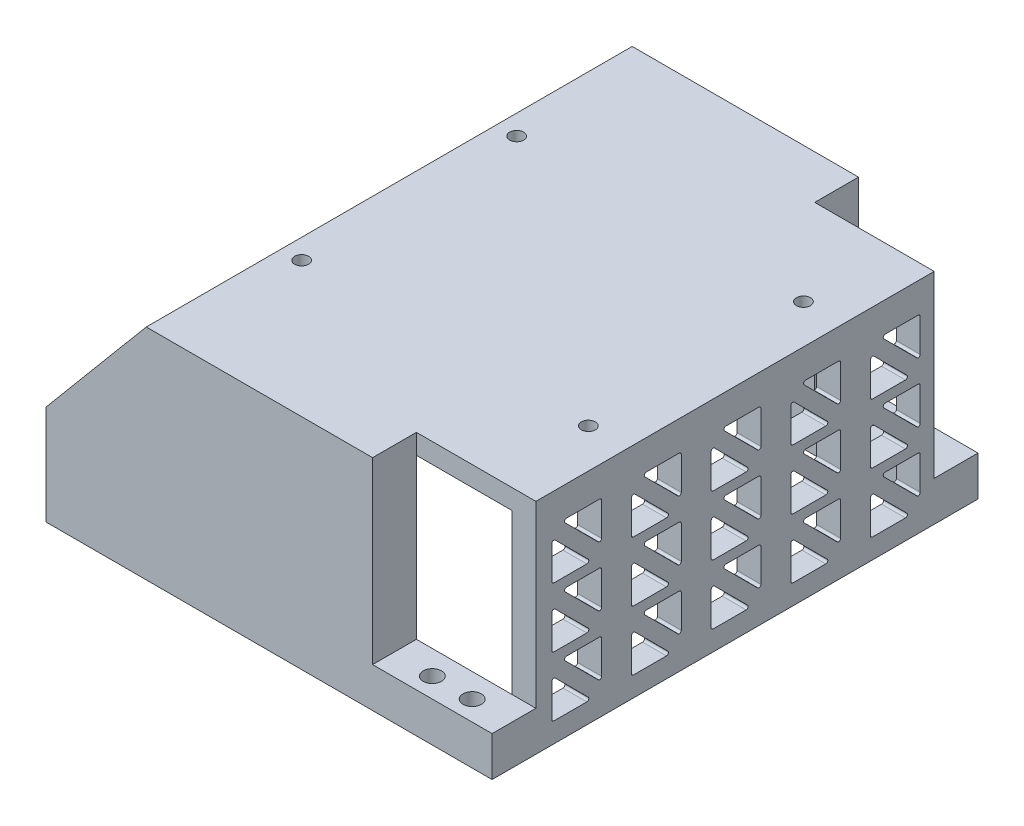
SolidWorks part; units mm, degrees
ref_plane "Front Plane" through (0, 0, 0) normal (0, 0, 1) x (1, 0, 0)
ref_plane "Top Plane" through (0, 0, 0) normal (0, 1, 0) x (1, 0, 0)
ref_plane "Right Plane" through (0, 0, 0) normal (1, 0, 0) x (0, 0, -1)
sketch "Sketch1" plane through (0, 0, 0) normal (0, 1, 0) x (1, 0, 0)
  line L0 (56, 61) -> (64.4545, 61) construction
  line L1 (0, 0) -> (112, 0)
  line L2 (0, 0) -> (0, 122)
  line L3 (0, 122) -> (112, 122)
  line L4 (112, 0) -> (112, 122)
  line L5 (0, 0) -> (112, 122) construction
  line L6 (0, 122) -> (112, 0) construction
  line L7 (106, 11) -> (112, 11)
  line L13 (26, 11) -> (106, 11)
  line L14 (82, 11) -> (82, 0)
  line L15 (82, 111) -> (82, 122)
  line L16 (106, 111) -> (112, 111)
  line L17 (26, 11) -> (26, 111)
  line L18 (26, 111) -> (106, 111)
  line L19 (106, 11) -> (106, 111)
  line L20 (26, 11) -> (106, 111) construction
  line L21 (26, 111) -> (106, 11) construction
  circle A0 centre (102, 5) radius 2.3
  circle A1 centre (92, 5) radius 2.3
  circle A2 centre (92, 117) radius 2.3
  circle A3 centre (102, 117) radius 2.3
  point P4 (56, 61)
  point P28 (66, 61)
  point P29 (0, 0)
  point P30 (0, 0)
  point P31 (0, 0)
  dimension "D3" = 4.6
  dimension "D1" = 122
  dimension "D2" = 112
  dimension "D4" = 10
  dimension "D5" = 5
  dimension "D6" = 10
  dimension "D7" = 100
  dimension "D8" = 80
  dimension "D9" = 30
extrude "Boss-Extrude1" add sketch "Sketch1" along normal blind 50 contours L15 L3 L2 L1 L14 | L16 L7 L4 region at (24.4696, 0, -61) region at (109, 0, -61)
extrude "Boss-Extrude2" add sketch "Sketch1<3>" along normal blind 10 contours L16 L4 L3 L15 A2 A3 | L14 L1 L4 L7 A1 A0 region at (97, 0, -5.556) region at (97, 0, -116.444)
sketch "Sketch1<3>" plane through (0, 0, 0) normal (0, 1, 0) x (1, 0, 0) same geometry as "Sketch1"
sketch "Sketch2" plane through (112, 0, 0) normal (1, 0, 0) x (0, 0, -1)
  line L54 (0, 0) -> (122, 0) construction
  line L55 (11, 50) -> (111, 50) construction
  line L56 (11, 50) -> (11, 0) construction
  line L57 (11, 0) -> (111, 0) construction
  line L58 (111, 50) -> (111, 0) construction
  line L59 (11, 50) -> (111, 0) construction
  line L60 (11, 0) -> (111, 50) construction
  line L61 (111, 50) -> (111, 10) construction
  line L62 (15, 35.5) -> (15, 43.7929)
  line L63 (15.8536, 44.1464) -> (24.1464, 35.8536)
  line L64 (23.7929, 35) -> (15.5, 35)
  line L65 (27.5, 38.7071) -> (27.5, 47)
  line L66 (27, 47.5) -> (18.7071, 47.5)
  line L67 (18.3536, 46.6464) -> (26.6464, 38.3536)
  line L68 (43.7929, 35) -> (35.5, 35)
  line L69 (15, 35) -> (27.5, 35) construction
  line L70 (15, 35) -> (15, 47.5) construction
  line L71 (15, 47.5) -> (27.5, 47.5) construction
  line L72 (27.5, 35) -> (27.5, 47.5) construction
  line L73 (15, 35) -> (27.5, 47.5) construction
  line L74 (15, 47.5) -> (27.5, 35) construction
  line L75 (35, 35.5) -> (35, 43.7929)
  line L76 (35.8536, 44.1464) -> (44.1464, 35.8536)
  line L77 (38.3536, 46.6464) -> (46.6464, 38.3536)
  line L78 (47.5, 38.7071) -> (47.5, 47)
  line L79 (47, 47.5) -> (38.7071, 47.5)
  line L80 (63.7929, 35) -> (55.5, 35)
  line L81 (55, 35.5) -> (55, 43.7929)
  line L82 (55.8536, 44.1464) -> (64.1464, 35.8536)
  line L83 (58.3536, 46.6464) -> (66.6464, 38.3536)
  line L84 (67.5, 38.7071) -> (67.5, 47)
  line L85 (67, 47.5) -> (58.7071, 47.5)
  line L86 (83.7929, 35) -> (75.5, 35)
  line L87 (75, 35.5) -> (75, 43.7929)
  line L88 (75.8536, 44.1464) -> (84.1464, 35.8536)
  line L89 (78.3536, 46.6464) -> (86.6464, 38.3536)
  line L90 (87.5, 38.7071) -> (87.5, 47)
  line L91 (87, 47.5) -> (78.7071, 47.5)
  line L92 (103.7929, 35) -> (95.5, 35)
  line L93 (95, 35.5) -> (95, 43.7929)
  line L94 (95.8536, 44.1464) -> (104.1464, 35.8536)
  line L95 (98.3536, 46.6464) -> (106.6464, 38.3536)
  line L96 (107.5, 38.7071) -> (107.5, 47)
  line L97 (107, 47.5) -> (98.7071, 47.5)
  line L98 (43.7929, 20) -> (35.5, 20)
  line L99 (35, 20.5) -> (35, 28.7929)
  line L100 (35.8536, 29.1464) -> (44.1464, 20.8536)
  line L101 (38.3536, 31.6464) -> (46.6464, 23.3536)
  line L102 (47.5, 23.7071) -> (47.5, 32)
  line L103 (47, 32.5) -> (38.7071, 32.5)
  line L104 (63.7929, 20) -> (55.5, 20)
  line L105 (55, 20.5) -> (55, 28.7929)
  line L106 (55.8536, 29.1464) -> (64.1464, 20.8536)
  line L107 (58.3536, 31.6464) -> (66.6464, 23.3536)
  line L108 (67.5, 23.7071) -> (67.5, 32)
  line L109 (67, 32.5) -> (58.7071, 32.5)
  line L110 (83.7929, 20) -> (75.5, 20)
  line L111 (75, 20.5) -> (75, 28.7929)
  line L112 (75.8536, 29.1464) -> (84.1464, 20.8536)
  line L113 (78.3536, 31.6464) -> (86.6464, 23.3536)
  line L114 (87.5, 23.7071) -> (87.5, 32)
  line L115 (87, 32.5) -> (78.7071, 32.5)
  line L116 (103.7929, 20) -> (95.5, 20)
  line L117 (95, 20.5) -> (95, 28.7929)
  line L118 (95.8536, 29.1464) -> (104.1464, 20.8536)
  line L119 (98.3536, 31.6464) -> (106.6464, 23.3536)
  line L120 (107.5, 23.7071) -> (107.5, 32)
  line L121 (107, 32.5) -> (98.7071, 32.5)
  line L122 (43.7929, 5) -> (35.5, 5)
  line L123 (35, 5.5) -> (35, 13.7929)
  line L124 (35.8536, 14.1464) -> (44.1464, 5.8536)
  line L125 (38.3536, 16.6464) -> (46.6464, 8.3536)
  line L126 (47.5, 8.7071) -> (47.5, 17)
  line L127 (47, 17.5) -> (38.7071, 17.5)
  line L128 (63.7929, 5) -> (55.5, 5)
  line L129 (55, 5.5) -> (55, 13.7929)
  line L130 (55.8536, 14.1464) -> (64.1464, 5.8536)
  line L131 (58.3536, 16.6464) -> (66.6464, 8.3536)
  line L132 (67.5, 8.7071) -> (67.5, 17)
  line L133 (67, 17.5) -> (58.7071, 17.5)
  line L134 (83.7929, 5) -> (75.5, 5)
  line L135 (75, 5.5) -> (75, 13.7929)
  line L136 (75.8536, 14.1464) -> (84.1464, 5.8536)
  line L137 (78.3536, 16.6464) -> (86.6464, 8.3536)
  line L138 (87.5, 8.7071) -> (87.5, 17)
  line L139 (87, 17.5) -> (78.7071, 17.5)
  line L140 (103.7929, 5) -> (95.5, 5)
  line L141 (95, 5.5) -> (95, 13.7929)
  line L142 (95.8536, 14.1464) -> (104.1464, 5.8536)
  line L143 (98.3536, 16.6464) -> (106.6464, 8.3536)
  line L144 (107.5, 8.7071) -> (107.5, 17)
  line L145 (107, 17.5) -> (98.7071, 17.5)
  line L146 (23.7929, 20) -> (15.5, 20)
  line L147 (15, 20.5) -> (15, 28.7929)
  line L148 (15.8536, 29.1464) -> (24.1464, 20.8536)
  line L149 (18.3536, 31.6464) -> (26.6464, 23.3536)
  line L150 (27.5, 23.7071) -> (27.5, 32)
  line L151 (27, 32.5) -> (18.7071, 32.5)
  line L152 (23.7929, 5) -> (15.5, 5)
  line L153 (15, 5.5) -> (15, 13.7929)
  line L154 (15.8536, 14.1464) -> (24.1464, 5.8536)
  line L155 (18.3536, 16.6464) -> (26.6464, 8.3536)
  line L156 (27.5, 8.7071) -> (27.5, 17)
  line L157 (27, 17.5) -> (18.7071, 17.5)
  line L158 (23.7929, 35) -> (43.7929, 35) construction
  line L159 (23.7929, 35) -> (23.7929, 20) construction
  arc A0 (27, 47.5) -> (27.5, 47) centre (27, 47) cw
  arc A1 (27.5, 38.7071) -> (26.6464, 38.3536) centre (27, 38.7071) cw
  arc A2 (24.1464, 35.8536) -> (23.7929, 35) centre (23.7929, 35.5) cw
  arc A3 (15, 35.5) -> (15.5, 35) centre (15.5, 35.5) ccw
  arc A4 (15, 43.7929) -> (15.8536, 44.1464) centre (15.5, 43.7929) cw
  arc A5 (18.7071, 47.5) -> (18.3536, 46.6464) centre (18.7071, 47) ccw
  arc A6 (35, 35.5) -> (35.5, 35) centre (35.5, 35.5) ccw
  arc A7 (44.1464, 35.8536) -> (43.7929, 35) centre (43.7929, 35.5) cw
  arc A8 (35, 43.7929) -> (35.8536, 44.1464) centre (35.5, 43.7929) cw
  arc A9 (38.7071, 47.5) -> (38.3536, 46.6464) centre (38.7071, 47) ccw
  arc A10 (47.5, 38.7071) -> (46.6464, 38.3536) centre (47, 38.7071) cw
  arc A11 (47, 47.5) -> (47.5, 47) centre (47, 47) cw
  arc A12 (55, 35.5) -> (55.5, 35) centre (55.5, 35.5) ccw
  arc A13 (64.1464, 35.8536) -> (63.7929, 35) centre (63.7929, 35.5) cw
  arc A14 (55, 43.7929) -> (55.8536, 44.1464) centre (55.5, 43.7929) cw
  arc A15 (58.7071, 47.5) -> (58.3536, 46.6464) centre (58.7071, 47) ccw
  arc A16 (67.5, 38.7071) -> (66.6464, 38.3536) centre (67, 38.7071) cw
  arc A17 (67, 47.5) -> (67.5, 47) centre (67, 47) cw
  arc A18 (75, 35.5) -> (75.5, 35) centre (75.5, 35.5) ccw
  arc A19 (84.1464, 35.8536) -> (83.7929, 35) centre (83.7929, 35.5) cw
  arc A20 (75, 43.7929) -> (75.8536, 44.1464) centre (75.5, 43.7929) cw
  arc A21 (78.7071, 47.5) -> (78.3536, 46.6464) centre (78.7071, 47) ccw
  arc A22 (87.5, 38.7071) -> (86.6464, 38.3536) centre (87, 38.7071) cw
  arc A23 (87, 47.5) -> (87.5, 47) centre (87, 47) cw
  arc A24 (95, 35.5) -> (95.5, 35) centre (95.5, 35.5) ccw
  arc A25 (104.1464, 35.8536) -> (103.7929, 35) centre (103.7929, 35.5) cw
  arc A26 (95, 43.7929) -> (95.8536, 44.1464) centre (95.5, 43.7929) cw
  arc A27 (98.7071, 47.5) -> (98.3536, 46.6464) centre (98.7071, 47) ccw
  arc A28 (107.5, 38.7071) -> (106.6464, 38.3536) centre (107, 38.7071) cw
  arc A29 (107, 47.5) -> (107.5, 47) centre (107, 47) cw
  arc A30 (35, 20.5) -> (35.5, 20) centre (35.5, 20.5) ccw
  arc A31 (44.1464, 20.8536) -> (43.7929, 20) centre (43.7929, 20.5) cw
  arc A32 (35, 28.7929) -> (35.8536, 29.1464) centre (35.5, 28.7929) cw
  arc A33 (38.7071, 32.5) -> (38.3536, 31.6464) centre (38.7071, 32) ccw
  arc A34 (47.5, 23.7071) -> (46.6464, 23.3536) centre (47, 23.7071) cw
  arc A35 (47, 32.5) -> (47.5, 32) centre (47, 32) cw
  arc A36 (55, 20.5) -> (55.5, 20) centre (55.5, 20.5) ccw
  arc A37 (64.1464, 20.8536) -> (63.7929, 20) centre (63.7929, 20.5) cw
  arc A38 (55, 28.7929) -> (55.8536, 29.1464) centre (55.5, 28.7929) cw
  arc A39 (58.7071, 32.5) -> (58.3536, 31.6464) centre (58.7071, 32) ccw
  arc A40 (67.5, 23.7071) -> (66.6464, 23.3536) centre (67, 23.7071) cw
  arc A41 (67, 32.5) -> (67.5, 32) centre (67, 32) cw
  arc A42 (75, 20.5) -> (75.5, 20) centre (75.5, 20.5) ccw
  arc A43 (84.1464, 20.8536) -> (83.7929, 20) centre (83.7929, 20.5) cw
  arc A44 (75, 28.7929) -> (75.8536, 29.1464) centre (75.5, 28.7929) cw
  arc A45 (78.7071, 32.5) -> (78.3536, 31.6464) centre (78.7071, 32) ccw
  arc A46 (87.5, 23.7071) -> (86.6464, 23.3536) centre (87, 23.7071) cw
  arc A47 (87, 32.5) -> (87.5, 32) centre (87, 32) cw
  arc A48 (95, 20.5) -> (95.5, 20) centre (95.5, 20.5) ccw
  arc A49 (104.1464, 20.8536) -> (103.7929, 20) centre (103.7929, 20.5) cw
  arc A50 (95, 28.7929) -> (95.8536, 29.1464) centre (95.5, 28.7929) cw
  arc A51 (98.7071, 32.5) -> (98.3536, 31.6464) centre (98.7071, 32) ccw
  arc A52 (107.5, 23.7071) -> (106.6464, 23.3536) centre (107, 23.7071) cw
  arc A53 (107, 32.5) -> (107.5, 32) centre (107, 32) cw
  arc A54 (35, 5.5) -> (35.5, 5) centre (35.5, 5.5) ccw
  arc A55 (44.1464, 5.8536) -> (43.7929, 5) centre (43.7929, 5.5) cw
  arc A56 (35, 13.7929) -> (35.8536, 14.1464) centre (35.5, 13.7929) cw
  arc A57 (38.7071, 17.5) -> (38.3536, 16.6464) centre (38.7071, 17) ccw
  arc A58 (47.5, 8.7071) -> (46.6464, 8.3536) centre (47, 8.7071) cw
  arc A59 (47, 17.5) -> (47.5, 17) centre (47, 17) cw
  arc A60 (55, 5.5) -> (55.5, 5) centre (55.5, 5.5) ccw
  arc A61 (64.1464, 5.8536) -> (63.7929, 5) centre (63.7929, 5.5) cw
  arc A62 (55, 13.7929) -> (55.8536, 14.1464) centre (55.5, 13.7929) cw
  arc A63 (58.7071, 17.5) -> (58.3536, 16.6464) centre (58.7071, 17) ccw
  arc A64 (67.5, 8.7071) -> (66.6464, 8.3536) centre (67, 8.7071) cw
  arc A65 (67, 17.5) -> (67.5, 17) centre (67, 17) cw
  arc A66 (75, 5.5) -> (75.5, 5) centre (75.5, 5.5) ccw
  arc A67 (84.1464, 5.8536) -> (83.7929, 5) centre (83.7929, 5.5) cw
  arc A68 (75, 13.7929) -> (75.8536, 14.1464) centre (75.5, 13.7929) cw
  arc A69 (78.7071, 17.5) -> (78.3536, 16.6464) centre (78.7071, 17) ccw
  arc A70 (87.5, 8.7071) -> (86.6464, 8.3536) centre (87, 8.7071) cw
  arc A71 (87, 17.5) -> (87.5, 17) centre (87, 17) cw
  arc A72 (95, 5.5) -> (95.5, 5) centre (95.5, 5.5) ccw
  arc A73 (104.1464, 5.8536) -> (103.7929, 5) centre (103.7929, 5.5) cw
  arc A74 (95, 13.7929) -> (95.8536, 14.1464) centre (95.5, 13.7929) cw
  arc A75 (98.7071, 17.5) -> (98.3536, 16.6464) centre (98.7071, 17) ccw
  arc A76 (107.5, 8.7071) -> (106.6464, 8.3536) centre (107, 8.7071) cw
  arc A77 (107, 17.5) -> (107.5, 17) centre (107, 17) cw
  arc A78 (15, 20.5) -> (15.5, 20) centre (15.5, 20.5) ccw
  arc A79 (24.1464, 20.8536) -> (23.7929, 20) centre (23.7929, 20.5) cw
  arc A80 (15, 28.7929) -> (15.8536, 29.1464) centre (15.5, 28.7929) cw
  arc A81 (18.7071, 32.5) -> (18.3536, 31.6464) centre (18.7071, 32) ccw
  arc A82 (27.5, 23.7071) -> (26.6464, 23.3536) centre (27, 23.7071) cw
  arc A83 (27, 32.5) -> (27.5, 32) centre (27, 32) cw
  arc A84 (15, 5.5) -> (15.5, 5) centre (15.5, 5.5) ccw
  arc A85 (24.1464, 5.8536) -> (23.7929, 5) centre (23.7929, 5.5) cw
  arc A86 (15, 13.7929) -> (15.8536, 14.1464) centre (15.5, 13.7929) cw
  arc A87 (18.7071, 17.5) -> (18.3536, 16.6464) centre (18.7071, 17) ccw
  arc A88 (27.5, 8.7071) -> (26.6464, 8.3536) centre (27, 8.7071) cw
  arc A89 (27, 17.5) -> (27.5, 17) centre (27, 17) cw
  point P4 (61, 25)
  point P18 (21.25, 41.25)
  point P21 (27.5, 47.5)
  point P31 (15, 45)
  point P34 (17.5, 47.5)
  dimension "D7" = 0.5
  dimension "D1" = 10
  dimension "D2" = 4
  dimension "D3" = 5
  dimension "D4" = 10
  dimension "D5" = 12.5
  dimension "D6" = 12.5
  dimension "D10" = 20
  dimension "D11" = 15
  dimension "D8" = 5
  dimension "D9" = 3
extrude "Cut-Extrude1" cut sketch "Sketch2" against normal up to surface (6 mm away) up to face at (106, 20, -61)
sketch "Sketch3" plane through (0, 50, 0) normal (0, 1, 0) x (1, 0, 0)
  line L0 (112, 11) -> (82, 11)
  line L1 (0, 122) -> (82, 122)
  line L2 (0, 122) -> (0, 0)
  line L3 (0, 0) -> (82, 0)
  line L4 (112, 111) -> (112, 11)
  line L7 (82, 11) -> (82, 0)
  line L8 (112, 111) -> (82, 111)
  line L9 (82, 111) -> (82, 122)
  point P1 (0, 0)
  point P3 (0, 0)
extrude "Boss-Extrude3" add sketch "Sketch3" along normal blind 5
chamfer "Chamfer1" distance 30 angle 40 1 edges at (0, 55, -61) first distance on face at (0, 27.5, -61)
sketch "Sketch4" plane through (0, 55, 0) normal (0, 1, 0) x (1, 0, 0)
  line L0 (25.173, 61) -> (30.173, 61) construction
  line L1 (30.173, 34) -> (102.173, 34) construction
  line L2 (30.173, 34) -> (30.173, 88) construction
  line L3 (30.173, 88) -> (102.173, 88) construction
  line L4 (102.173, 34) -> (102.173, 88) construction
  line L5 (30.173, 34) -> (102.173, 88) construction
  line L6 (30.173, 88) -> (102.173, 34) construction
  line L7 (25.173, 122) -> (25.173, 0) construction
  circle A0 centre (30.173, 88) radius 1.75
  circle A1 centre (102.173, 88) radius 1.75
  circle A2 centre (102.173, 34) radius 1.75
  circle A3 centre (30.173, 34) radius 1.75
  point P4 (66.173, 61)
  dimension "D3" = 3.5
  dimension "D1" = 72
  dimension "D2" = 54
  dimension "D4" = 5
extrude "Cut-Extrude2" cut sketch "Sketch4" against normal up to next
sketch "Sketch5" plane through (0, 0, 0) normal (0, 0, 1) x (1, 0, 0)
  line L0 (3, 23.9081) -> (25.173, 50)
  line L3 (26.4176, 3) -> (26.4176, 50)
  line L4 (25.173, 50) -> (82, 50)
  line L5 (25.173, 50) -> (82, 50)
  line L6 (26.4176, 50) -> (25.173, 50)
  line L7 (26.4176, 3) -> (25.173, 3)
  line L25 (3, 3) -> (112, 3)
  line L26 (3, 23.9081) -> (3, 3)
  line L27 (27.4711, 53.0716) -> (3, 23.9081)
  line L28 (3, 3) -> (25.173, 3)
  line L29 (3, 23.9081) -> (3, 3)
  dimension "D1" = 5
  dimension "D2" = 3
extrude "Cut-Extrude3" cut sketch "Sketch5" against normal up to surface (111 mm away) from offset 11 contours L0 L29 L28 L7 L3 L5 region at (16.2482, 21.2225, 0) up to face at (71.3333, 20, -111) offset against normal yes
